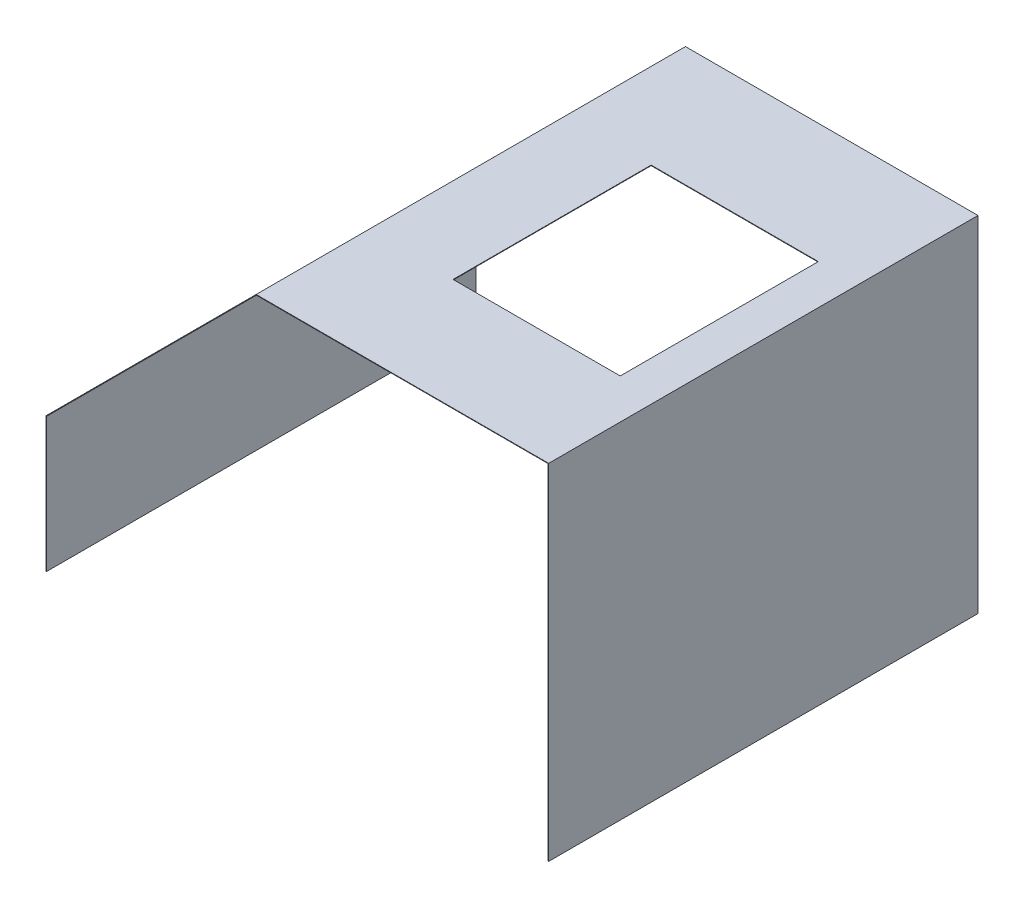
SolidWorks part; units mm, degrees
other "Carpeta de soldadura"
ref_plane "Alzado" through (0, 0, 0) normal (0, 0, 1) x (1, 0, 0)
ref_plane "Planta" through (0, 0, 0) normal (0, 1, 0) x (1, 0, 0)
ref_plane "Vista lateral" through (0, 0, 0) normal (1, 0, 0) x (0, 0, -1)
sketch "Croquis1" plane through (0, 0, 0) normal (0, 0, 1) x (1, 0, 0)
  line L0 (0, 0) -> (765, 0)
  line L1 (765, 0) -> (765, 525)
  line L2 (765, 525) -> (320, 525)
  line L3 (320, 525) -> (0, 205)
  line L4 (0, 205) -> (0, 0)
  dimension "D1" = 765
  dimension "D2" = 525
  dimension "D3" = 445
  dimension "D4" = 205
extrude "Saliente-Extruir1" add sketch "Croquis1" along normal blind 0.8357
sketch "Croquis2" plane through (0, 0, 0.8357) normal (0, 0, 1) x (1, 0, 0)
  line L15 (765.8357, 525.8357) -> (319.6539, 525.8357)
  line L16 (319.6539, 525.8357) -> (-0.8357, 205.3461)
  line L22 (-0.8357, 205.3461) -> (-0.8357, 0)
  line L24 (765.8357, 0) -> (765.8357, 525.8357)
  line L25 (0, 205) -> (0, 0)
  line L26 (0, 0) -> (765, 0)
  line L27 (765, 0) -> (765, 525)
  line L28 (765, 525) -> (320, 525)
  line L29 (320, 525) -> (0, 205)
  line L30 (0, 205) -> (0, 0)
  line L32 (765, 0) -> (765, 525)
  line L33 (765, 525) -> (320, 525)
  line L34 (320, 525) -> (0, 205)
  line L35 (0, 0) -> (-0.8357, 0)
  line L36 (-0.8357, 205.3461) -> (-0.8357, -0.8357) construction
  line L37 (-0.8357, -0.8357) -> (765.8357, -0.8357) construction
  line L38 (0, 0) -> (765, 0) construction
  line L39 (765, 0) -> (765.8357, 0)
  line L40 (765.8357, -0.8357) -> (765.8357, 525.8357) construction
  dimension "D1" = 0
  dimension "D2" = 0.8357
extrude "Saliente-Extruir2" add sketch "Croquis2" along normal blind 12.7
ref_plane "Plano1" through (0, 0, 13.5357) normal (0, 0, 1) x (1, 0, 0)
sketch "Croquis3" plane through (0, 0, 13.5357) normal (0, 0, 1) x (1, 0, 0)
  line L0 (450, 525.8357) -> (450, 525)
  line L1 (765.8357, 0) -> (765.8357, 525.8357) construction
  line L2 (765.8357, 0) -> (765.8357, 525.8357)
  line L3 (450, 525) -> (320, 525)
  line L5 (320, 525) -> (0, 205)
  line L6 (765.8357, 525.8357) -> (319.6539, 525.8357) construction
  line L7 (765, 525) -> (765, 0)
  line L8 (765, 0) -> (765.8357, 0)
  line L9 (765, 525) -> (705, 525)
  line L10 (320, 525) -> (765, 525) construction
  line L11 (705, 525) -> (705, 525.8357)
  line L12 (705, 525.8357) -> (765.8357, 525.8357)
  line L13 (0, 205) -> (0, 0)
  line L14 (0, 0) -> (-0.8357, 0)
  line L15 (-0.8357, 0) -> (-0.8357, 205.3461)
  line L16 (-0.8357, 205.3461) -> (319.6539, 525.8357)
  line L17 (319.6539, 525.8357) -> (450, 525.8357)
  dimension "D1" = 130
  dimension "D2" = 255
extrude "Saliente-Extruir3" add sketch "Croquis3" along normal blind 642.126
sketch "Croquis4" plane through (0, 0, 13.5357) normal (0, 0, 1) x (1, 0, 0)
  line L4 (705, 525.8357) -> (450, 525.8357)
  line L5 (450, 525.8357) -> (450, 525)
  line L6 (450, 525) -> (705, 525)
  line L7 (705, 525) -> (705, 525.8357)
  line L8 (705, 525.8357) -> (450, 525.8357)
  line L9 (450, 525.8357) -> (450, 525)
  line L10 (450, 525) -> (705, 525)
  line L11 (705, 525) -> (705, 525.8357)
  dimension "D1" = 0
extrude "Saliente-Extruir4" add sketch "Croquis4" along normal blind 170
sketch "Croquis5" plane through (0, 0, 655.6617) normal (0, 0, 1) x (1, 0, 0)
  line L4 (705, 525) -> (705, 525.8357)
  line L5 (705, 525.8357) -> (450, 525.8357)
  line L6 (450, 525.8357) -> (450, 525)
  line L7 (450, 525) -> (705, 525)
  line L8 (705, 525) -> (705, 525.8357)
  line L9 (705, 525.8357) -> (450, 525.8357)
  line L10 (450, 525.8357) -> (450, 525)
  line L11 (450, 525) -> (705, 525)
  dimension "D1" = 0
extrude "Saliente-Extruir5" add sketch "Croquis5" against normal blind 170
sketch "Croquis6" plane through (-103.0909, 103.0909, 0) normal (-0.7071, 0.7071, 0) x (0, 0, 1)
  line L0 (0.8357, 597.8514) -> (655.6617, 144.6107) construction
  line L1 (0.8357, 144.6107) -> (655.6617, 597.8514) construction
  line L2 (655.6617, 597.8514) -> (0.8357, 597.8514) construction
  line L3 (43.2487, 545.8514) -> (613.2487, 545.8514) construction
  line L4 (43.2487, 545.8514) -> (43.2487, 196.6107) construction
  line L5 (43.2487, 196.6107) -> (613.2487, 196.6107) construction
  line L6 (613.2487, 545.8514) -> (613.2487, 196.6107) construction
  line L7 (43.2487, 545.8514) -> (613.2487, 196.6107) construction
  line L8 (43.2487, 196.6107) -> (613.2487, 545.8514) construction
  line L9 (43.2487, 196.6107) -> (613.2487, 196.6107)
  line L10 (43.2487, 196.6107) -> (43.2487, 597.8514)
  line L11 (43.2487, 597.8514) -> (613.2487, 597.8514)
  line L12 (613.2487, 196.6107) -> (613.2487, 597.8514)
  line L13 (655.6617, 144.6107) -> (0.8357, 144.6107) construction
  point P8 (328.2487, 371.2311)
  dimension "D1" = 52
  dimension "D2" = 570
extrude "Cortar-Extruir1" cut sketch "Croquis6" against normal blind 190
sketch "Croquis7" plane through (0, 0, 0.8357) normal (0, 0, 1) x (1, 0, 0)
  line L0 (0, 0) -> (765, 0)
  line L1 (765, 0) -> (765, 525)
  line L2 (765, 525) -> (320, 525)
  line L3 (320, 525) -> (0, 205)
  line L4 (0, 205) -> (0, 0)
extrude "Cortar-Extruir2" cut sketch "Croquis7" against normal blind 174 and the other way blind 198
